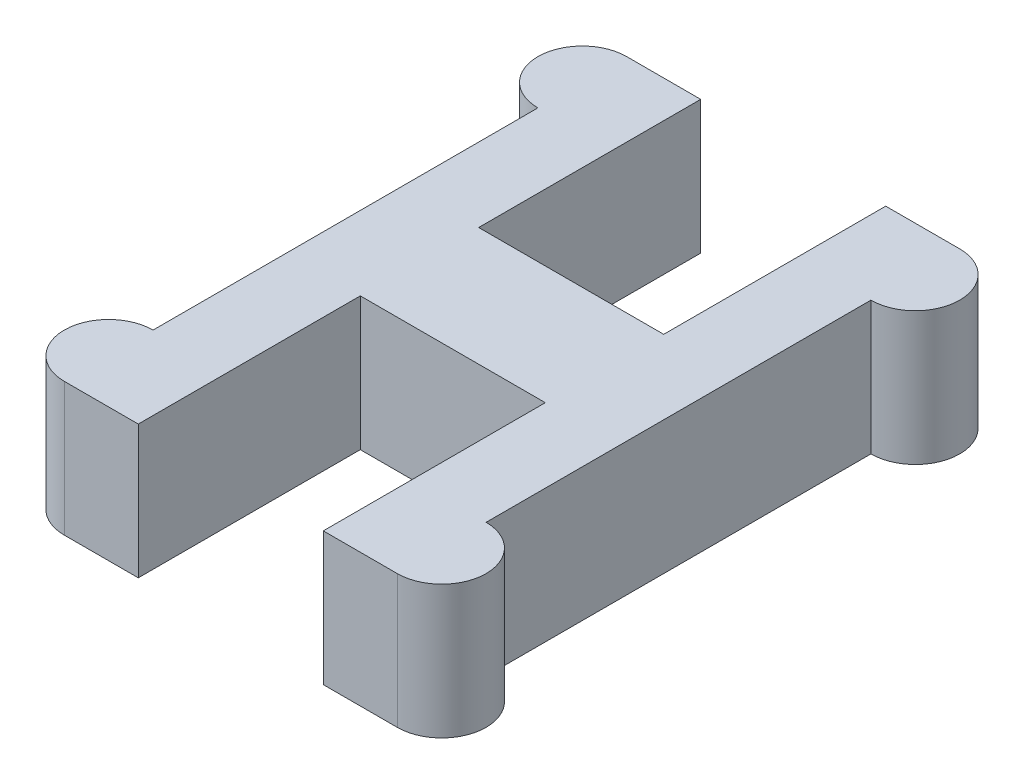
SolidWorks part; units mm, degrees
ref_plane "Front Plane" through (0, 0, 0) normal (0, 0, 1) x (1, 0, 0)
ref_plane "Top Plane" through (0, 0, 0) normal (0, 1, 0) x (1, 0, 0)
ref_plane "Right Plane" through (0, 0, 0) normal (1, 0, 0) x (0, 0, -1)
sketch "Sketch1" plane through (0, 0, 0) normal (0, 1, 0) x (1, 0, 0)
  line L0 (-2.25, 3.2) -> (2.25, 3.2) construction
  line L1 (-2.25, -3.8) -> (2.25, -3.8)
  line L2 (-2.25, -3.8) -> (-2.25, 3.8)
  line L3 (-2.25, 3.8) -> (2.25, 3.8)
  line L4 (2.25, -3.8) -> (2.25, 3.8)
  line L5 (-2.25, -3.8) -> (2.25, 3.8) construction
  line L6 (-2.25, 3.8) -> (2.25, -3.8) construction
  line L7 (-2.25, 3.8) -> (2.25, 3.8)
  line L8 (-2.25, 2.6) -> (2.25, 2.6)
  line L9 (-2.25, -3.2) -> (2.25, -3.2) construction
  line L10 (-2.25, -2.6) -> (2.25, -2.6)
  line L11 (-2.25, -3.8) -> (2.25, -3.8)
  line L13 (-1.25, 3.8) -> (1.25, 3.8)
  line L14 (-1.25, 3.8) -> (-1.25, 0.8)
  line L15 (-1.25, 0.8) -> (1.25, 0.8)
  line L16 (1.25, 3.8) -> (1.25, 0.8)
  line L17 (1.25, -3.8) -> (-1.25, -3.8)
  line L18 (1.25, -3.8) -> (1.25, -0.8)
  line L19 (1.25, -0.8) -> (-1.25, -0.8)
  line L20 (-1.25, -3.8) -> (-1.25, -0.8)
  arc A0 (-2.25, 3.8) -> (-2.25, 2.6) centre (-2.25, 3.2) ccw
  arc A1 (2.25, 2.6) -> (2.25, 3.8) centre (2.25, 3.2) ccw
  arc A2 (-2.25, -2.6) -> (-2.25, -3.8) centre (-2.25, -3.2) ccw
  arc A3 (2.25, -3.8) -> (2.25, -2.6) centre (2.25, -3.2) ccw
  point P0 (0, 0)
  point P8 (0, 3.2)
  point P15 (0, -3.2)
  point P28 (0, 0.8)
  point P29 (0, -0.8)
  dimension "D1" = 4.5
  dimension "D2" = 7.6
  dimension "D3" = 1.2
  dimension "D4" = 2.5
  dimension "D5" = 3
extrude "Boss-Extrude1" add sketch "Sketch1" along normal blind 1.8 contours L10 L20 L19 L18 L4 L8 L16 L15 L14 L2 | L14 L3 L2 L8 | L2 A0 | L3 L16 L8 L4 | L4 A1 | L4 A3 | L18 L1 L4 L10 | L1 L20 L10 L2 | L2 A2 region at (-1.75, 0, 3.2) region at (-2.5046, 0, 3.2) region at (0, 0, 0) region at (1.75, 0, 3.2) region at (-2.5046, 0, -3.2) region at (-1.75, 0, -3.2) region at (2.5046, 0, 3.2) region at (1.75, 0, -3.2) region at (2.5046, 0, -3.2)
